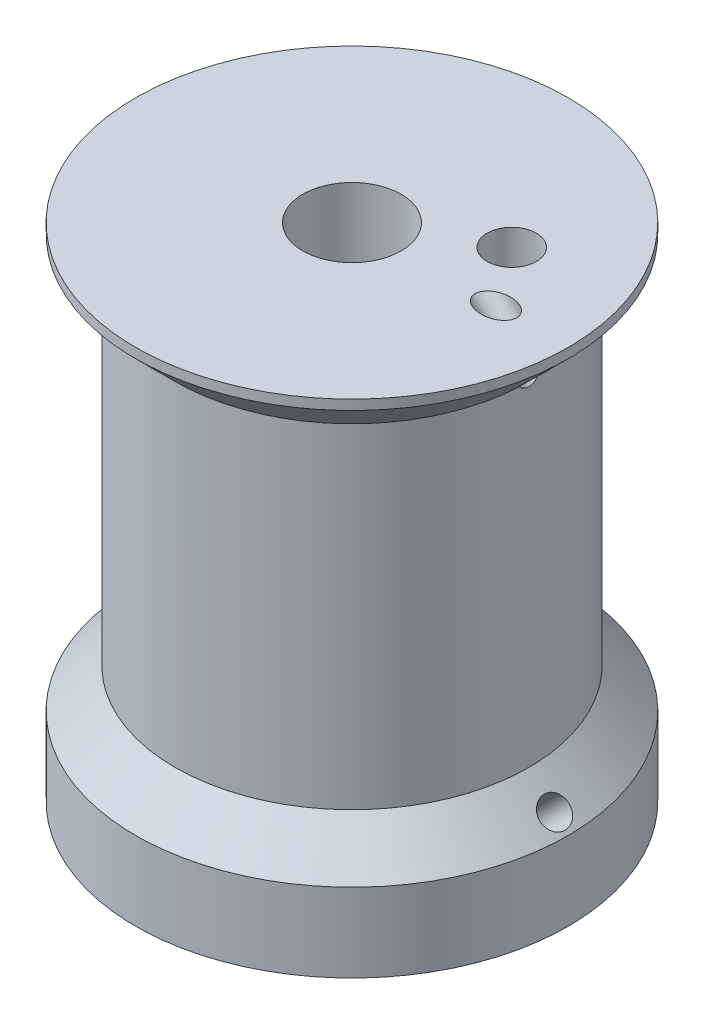
SolidWorks part; units mm, degrees
ref_plane "Front Plane" through (0, 0, 0) normal (0, 0, 1) x (1, 0, 0)
ref_plane "Top Plane" through (0, 0, 0) normal (0, 1, 0) x (1, 0, 0)
ref_plane "Right Plane" through (0, 0, 0) normal (1, 0, 0) x (0, 0, -1)
sketch "Sketch11" plane through (0, 0, 0) normal (0, 0, 1) x (1, 0, 0)
  line L0 (0, 0) -> (0, 25.5) construction
  line L1 (2.5, 25.5) -> (11, 25.5)
  line L2 (11, 25.5) -> (11, 25)
  line L3 (11, 25) -> (9, 23)
  line L4 (9, 23) -> (9, 6)
  line L5 (9, 6) -> (11, 4)
  line L6 (11, 4) -> (11, 0)
  line L7 (11, 0) -> (2.5, 0)
  line L8 (2.5, 0) -> (2.5, 25.5)
  line L9 (9, 16) -> (2.5, 16) construction
  point P13 (9, 16)
  dimension "D1" = 45
  dimension "D2" = 25.5
  dimension "D3" = 18
  dimension "D4" = 22
  dimension "D5" = 4
  dimension "D6" = 17
  dimension "D7" = 5
  dimension "D8" = 16
revolve "Revolve1" add sketch "Sketch11" angle 360 about L0
sketch "Sketch9" plane through (0, 0, 0) normal (0, -1, 0) x (1, 0, 0)
  line L0 (0, 0) -> (5.1529, -2.975) construction
  circle A0 centre (0, 0) radius 2.5 construction
  circle A1 centre (5.1529, -2.975) radius 1.25
  dimension "D1" = 5
  dimension "D2" = 2.5
  dimension "D3" = 2.2
  dimension "D4" = 30
extrude "Cut-Extrude2" cut sketch "Sketch9" against normal through all
sketch "Sketch10" plane through (0, 0, 0) normal (0, 0, 1) x (1, 0, 0)
  line L0 (10.313, 4.687) -> (5.626, 0) construction
  line L1 (10.4157, 22.4073) -> (9.8854, 21.877)
  line L2 (10.4157, 22.4073) -> (6.7927, 26.0303)
  line L3 (10.4157, 22.4073) -> (7.323, 25.5) construction
  line L4 (9.8854, 21.877) -> (6.2624, 25.5)
  line L5 (6.7927, 26.0303) -> (6.2624, 25.5)
  line L6 (11, 4) -> (9, 6) construction
  line L7 (11, 25.5) -> (-11, 25.5) construction
  line L8 (-11, 0) -> (11, 0) construction
  line L9 (8.0739, 23.6885) -> (8.6042, 24.2188) construction
  line L10 (10.1506, 22.1421) -> (6.5275, 25.7652) construction
  line L11 (10.313, 4.687) -> (9.7827, 5.2173)
  line L12 (10.313, 4.687) -> (5.0957, -0.5303)
  line L13 (9.7827, 5.2173) -> (4.5653, 0)
  line L14 (5.0957, -0.5303) -> (4.5653, 0)
  line L15 (7.174, 2.6087) -> (7.7043, 2.0783) construction
  line L16 (10.0478, 4.9522) -> (4.8305, -0.2652) construction
  point P60 (8.3391, 23.9537)
  point P84 (7.4392, 2.3435)
  dimension "D1" = 2.6
  dimension "D2" = 3.8
  dimension "D3" = 0.75
  dimension "D4" = 0.75
revolve "Cut-Revolve1" cut sketch "Sketch10" angle 360 about L12 region at (7.4392, 2.3435, 0)
revolve "Cut-Revolve2" cut sketch "Sketch10<3>" angle 360 about L2 region at (8.3391, 23.9537, 0)
sketch "Sketch10<3>" plane through (0, 0, 0) normal (0, 0, 1) x (1, 0, 0) same geometry as "Sketch10"
hole_wizard "M3x0.5 Tapped Hole1" positions "Sketch12" profile "Sketch13" tap size "M3x0.5" standard "ANSI Metric" end condition through all
sketch "Sketch12" plane through (0, 0, 0) normal (1, 0, 0) x (0, 0, -1)
  point P0 (0, 2)
  dimension "D1" = 2
sketch "Sketch13" plane through (0, 2, 0) normal (0, 1, 0) x (0, 0, -1)
  line L0 (0, 0) -> (0, 11)
  line L1 (0, 11) -> (1.25, 11)
  line L2 (1.25, 11) -> (1.25, 0)
  line L5 (1.25, 0) -> (0, 0)
  line L11 (0, -6.35) -> (0, 107.95) construction
  dimension "Thru Tap Drill Dia." = 2.5
  dimension "Thru Tap Drill Depth" = 11
cosmetic thread "Hole Thread1" parameters "D2"=3
ref_plane "Plane1" through (0, 16, 0) normal (0, 1, 0) x (1, 0, 0)
